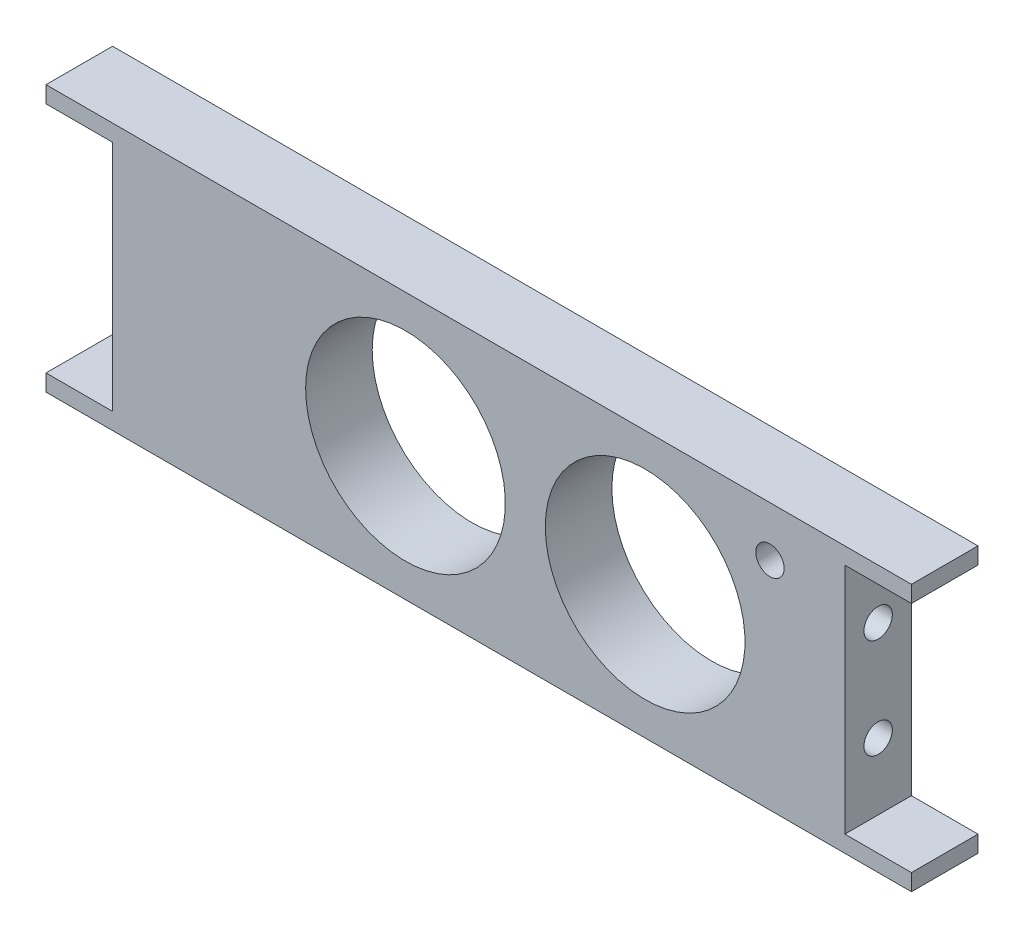
SolidWorks part; units mm, degrees
material "6061-T6 (SS)"
ref_plane "Front" through (0, 0, 0) normal (0, 0, 1) x (1, 0, 0)
ref_plane "Top" through (0, 0, 0) normal (0, 1, 0) x (1, 0, 0)
ref_plane "Right" through (0, 0, 0) normal (1, 0, 0) x (0, 0, -1)
sketch "Sketch1" plane through (0, 0, 0) normal (0, 0, 1) x (1, 0, 0)
  line L0 (0, 12.7) -> (0, -12.7) construction
  line L1 (-41.275, -12.7) -> (41.275, -12.7)
  line L2 (-41.275, -12.7) -> (-41.275, -11.1125)
  line L3 (-41.275, 12.7) -> (41.275, 12.7)
  line L4 (41.275, -12.7) -> (41.275, -11.1125)
  line L5 (-41.275, -12.7) -> (41.275, 12.7) construction
  line L6 (-41.275, 12.7) -> (41.275, -12.7) construction
  line L7 (-41.275, 11.1125) -> (-34.925, 11.1125)
  line L8 (41.275, 11.1125) -> (41.275, 12.7)
  line L9 (-41.275, -11.1125) -> (-34.925, -11.1125)
  line L10 (-34.925, 11.1125) -> (-34.925, -11.1125)
  line L11 (41.275, -11.1125) -> (34.925, -11.1125)
  line L12 (41.275, 11.1125) -> (34.925, 11.1125)
  line L13 (34.925, 11.1125) -> (34.925, -11.1125)
  line L14 (-41.275, 11.1125) -> (-41.275, 12.7)
  point P0 (0, 0)
  dimension "D1" = 82.55
  dimension "D2" = 25.4
  dimension "D3" = 1.5875
  dimension "D4" = 1.5875
  dimension "D5" = 6.35
extrude "Boss-Extrude1" add sketch "Sketch1" along normal blind 6.35
hole_wizard "Tap Drill for #6-32 Tap1" positions "Sketch3" profile "Sketch4" hole size "#6-32" standard "ANSI Inch"
sketch "Sketch3" plane through (34.925, 0, 0) normal (1, 0, 0) x (0, 0, -1)
  line L0 (-6.35, 12.7) -> (0, 12.7) construction
  line L1 (-6.35, -12.7) -> (0, -12.7) construction
  line L2 (-6.35, -11.1125) -> (0, -11.1125) construction
  point P0 (-3.175, 4.7625)
  point P2 (-3.175, -4.7625)
  point P12 (-3.175, -11.1125)
  dimension "D1" = 7.9375
  dimension "D2" = 7.9375
sketch "Sketch4" plane through (34.925, 4.7625, 3.175) normal (0, 1, 0) x (0, 0, -1)
  line L0 (0, 0) -> (0, 7.1627)
  line L1 (0, 7.1627) -> (1.3525, 6.35)
  line L2 (1.3525, 6.35) -> (1.3525, 0)
  line L5 (1.3525, 0) -> (0, 0)
  line L10 (0, 7.1627) -> (-1.3525, 6.35) construction
  line L11 (0, -6.35) -> (0, 107.95) construction
  dimension "Hole Dia." = 2.7051
  dimension "Hole Depth" = 6.35
  dimension "Drill Angle" = 118
ref_plane "Plane1" through (0, 0, 0) normal (-1, 0, 0) x (0, 0, 1)
mirror "Mirror1" about plane through (0, 0, 0) normal (-1, 0, 0) of "Tap Drill for #6-32 Tap1"
sketch "Sketch5" plane through (0, 0, 0) normal (0, 0, -1) x (-1, 0, 0)
  line L1 (-34.925, -11.1125) -> (-34.925, 11.1125) construction
  circle A0 centre (6.985, 0) radius 9.525
  circle A1 centre (-15.875, 0) radius 9.525
  dimension "D1" = 19.05
  dimension "D3" = 19.05
  dimension "D2" = 22.86
extrude "Cut-Extrude1" cut sketch "Sketch5" against normal through all
hole_wizard "Tap Drill for #6-32 Tap2" positions "Sketch7" profile "Sketch6" hole size "#6-32" standard "ANSI Inch" end condition through all
sketch "Sketch7" plane through (0, 0, 0) normal (0, 0, -1) x (-1, 0, 0)
  line L0 (-41.275, 12.7) -> (41.275, 12.7) construction
  line L1 (-34.925, -11.1125) -> (-34.925, 11.1125) construction
  point P0 (-27.7812, 7.9375)
  dimension "D1" = 4.7625
  dimension "D2" = 7.1437
sketch "Sketch6" plane through (27.7812, 7.9375, 0) normal (1, 0, 0) x (0, 1, 0)
  line L0 (0, 0) -> (0, 6.35)
  line L1 (0, 6.35) -> (1.3525, 6.35)
  line L2 (1.3525, 6.35) -> (1.3525, 0)
  line L5 (1.3525, 0) -> (0, 0)
  line L11 (0, -6.35) -> (0, 107.95) construction
  dimension "Thru Hole Dia." = 2.7051
  dimension "Thru Hole Depth" = 6.35
